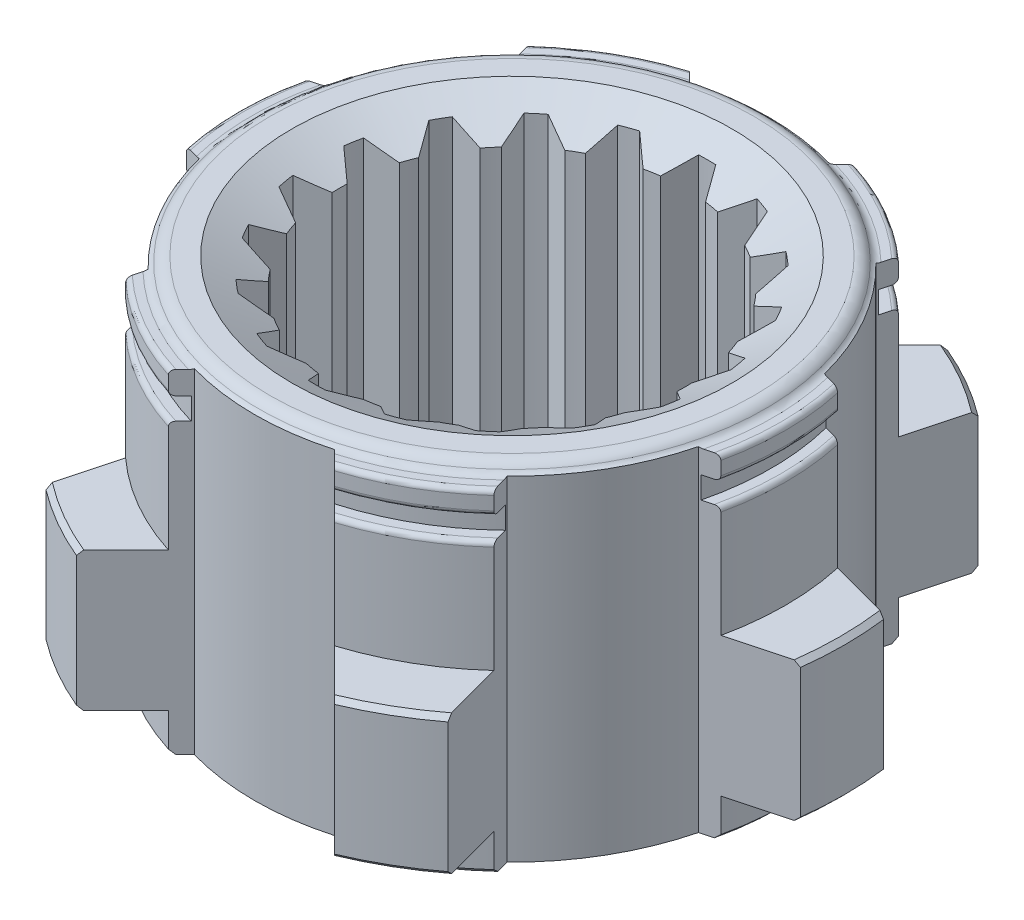
SolidWorks part; units mm, degrees
ref_plane "Plano frontal" through (0, 0, 0) normal (0, 0, 1) x (1, 0, 0)
ref_plane "Plano superior" through (0, 0, 0) normal (0, 1, 0) x (1, 0, 0)
ref_plane "Plano direito" through (0, 0, 0) normal (1, 0, 0) x (0, 0, -1)
sketch "Esboço1" plane through (0, 0, 0) normal (0, 0, 1) x (1, 0, 0)
  line L0 (0, -41.4943) -> (0, 46.6811) construction
  line L1 (18.1, 26.4164) -> (26.8, 26.4164)
  line L2 (26.8, 26.4164) -> (26.8, 25.4164)
  line L3 (26.8, 25.4164) -> (28.7, 25.4164)
  line L4 (28.7, 25.4164) -> (28.7, 23.0164)
  line L5 (28.7, 23.0164) -> (27.2, 23.0164)
  line L6 (27.2, 23.0164) -> (27.2, 20.7164)
  line L7 (27.2, 20.7164) -> (28.7, 20.7164)
  line L8 (28.7, 20.7164) -> (28.7, 9.0164)
  line L9 (28.7, 9.0164) -> (34.9, 9.0164)
  line L10 (34.9, 9.0164) -> (34.9, -5.5836)
  line L11 (34.9, -5.5836) -> (28.7, -5.5836)
  line L12 (28.7, -5.5836) -> (28.7, -9.5836)
  line L13 (28.7, -9.5836) -> (18.1, -9.5836)
  line L14 (18.1, -9.5836) -> (18.1, 26.4164)
  dimension "D1" = 18.1
  dimension "D2" = 26.8
  dimension "D3" = 28.7
  dimension "D4" = 27.2
  dimension "D5" = 28.7
  dimension "D6" = 34.9
  dimension "D7" = 28.7
  dimension "D8" = 1
  dimension "D9" = 2.3
  dimension "D10" = 11.7
  dimension "D11" = 16.4
  dimension "D12" = 14.6
  dimension "D13" = 36
revolve "Revolução1" add sketch "Esboço1" angle 360 about L0
chamfer "Chanfro1" distance 5 angle 30 1 edges at (0, 26.4164, -18.1) first distance on face at (0, 26.4164, -18.1)
chamfer "Chanfro2" distance 5 angle 30 1 edges at (0, -9.5836, -18.1) first distance on face at (0, -9.5836, -28.7)
fillet "Filete1" radius 1.5 1 edges at (0, 26.4164, -26.8)
fillet "Filete2" radius 1 1 edges at (0, 25.4164, -26.8)
fillet "Filete3" radius 0.5 3 edges at (0, 23.0164, -28.7) (0, 25.4164, -28.7) (0, 20.7164, -28.7)
chamfer "Chanfro3" distance 0.5 angle 45 3 edges at (0, -9.5836, -28.7) (0, -5.5836, -34.9) (0, 9.0164, -34.9)
sketch "Esboço2" plane through (0, -9.5836, 0) normal (0, -1, 0) x (1, 0, 0)
  line L0 (0, 0) -> (0, -44.3923) construction
  line L1 (-7.35, -25.9803) -> (-21.8141, -40.4444)
  line L2 (7.35, -25.9803) -> (21.8141, -40.4444)
  line L3 (-21.8141, -40.4444) -> (21.8141, -40.4444)
  line L4 (-26.1746, -6.6249) -> (-45.9329, -1.3307)
  line L5 (-18.8246, -19.3555) -> (-24.1188, -39.1137)
  line L6 (-45.9329, -1.3307) -> (-24.1188, -39.1137)
  line L7 (-18.8246, 19.3555) -> (-24.1188, 39.1137)
  line L8 (-26.1746, 6.6249) -> (-45.9329, 1.3307)
  line L9 (-24.1188, 39.1137) -> (-45.9329, 1.3307)
  line L10 (7.35, 25.9803) -> (21.8141, 40.4444)
  line L11 (-7.35, 25.9803) -> (-21.8141, 40.4444)
  line L12 (21.8141, 40.4444) -> (-21.8141, 40.4444)
  line L13 (26.1746, 6.6249) -> (45.9329, 1.3307)
  line L14 (18.8246, 19.3555) -> (24.1188, 39.1137)
  line L15 (45.9329, 1.3307) -> (24.1188, 39.1137)
  line L16 (18.8246, -19.3555) -> (24.1188, -39.1137)
  line L17 (26.1746, -6.6249) -> (45.9329, -1.3307)
  line L18 (24.1188, -39.1137) -> (45.9329, -1.3307)
  arc A0 (-26.1746, -6.6249) -> (-18.8246, -19.3555) centre (0, 0) ccw
  arc A1 (-7.35, -25.9803) -> (7.35, -25.9803) centre (0, 0) ccw
  arc A2 (-18.8246, 19.3555) -> (-26.1746, 6.6249) centre (0, 0) ccw
  arc A3 (7.35, 25.9803) -> (-7.35, 25.9803) centre (0, 0) ccw
  arc A4 (26.1746, 6.6249) -> (18.8246, 19.3555) centre (0, 0) ccw
  arc A5 (18.8246, -19.3555) -> (26.1746, -6.6249) centre (0, 0) ccw
  dimension "D1" = 6
  dimension "D2" = 90
extrude "Corte-extrusão1" cut sketch "Esboço2" against normal through all
sketch "Esboço3" plane through (0, 26.4164, 0) normal (0, 1, 0) x (1, 0, 0)
  line L0 (-0.9, 20.4802) -> (-2.4697, 17.7614)
  line L1 (0, 0) -> (0, 20.5) construction
  line L2 (0.9, 20.4802) -> (2.4697, 17.7614)
  line L3 (-2.4697, 17.7614) -> (2.4697, 17.7614)
  line L4 (6.1589, 19.5529) -> (3.754, 17.535)
  line L5 (7.8504, 18.9373) -> (8.3955, 15.8456)
  line L6 (3.754, 17.535) -> (8.3955, 15.8456)
  line L7 (12.475, 16.2673) -> (9.5249, 15.1935)
  line L8 (13.8539, 15.1103) -> (13.3087, 12.0185)
  line L9 (9.5249, 15.1935) -> (13.3087, 12.0185)
  line L10 (17.2864, 11.0195) -> (14.147, 11.0195)
  line L11 (18.1864, 9.4607) -> (16.6167, 6.7419)
  line L12 (14.147, 11.0195) -> (16.6167, 6.7419)
  line L13 (20.0128, 4.4427) -> (17.0627, 5.5164)
  line L14 (20.3254, 2.67) -> (17.9204, 0.6521)
  line L15 (17.0627, 5.5164) -> (17.9204, 0.6521)
  line L16 (20.3254, -2.67) -> (17.9204, -0.6521)
  line L17 (20.0128, -4.4427) -> (17.0627, -5.5164)
  line L18 (17.9204, -0.6521) -> (17.0627, -5.5164)
  line L19 (18.1864, -9.4607) -> (16.6167, -6.7419)
  line L20 (17.2864, -11.0195) -> (14.147, -11.0195)
  line L21 (16.6167, -6.7419) -> (14.147, -11.0195)
  line L22 (13.8539, -15.1103) -> (13.3087, -12.0185)
  line L23 (12.475, -16.2673) -> (9.5249, -15.1935)
  line L24 (13.3087, -12.0185) -> (9.5249, -15.1935)
  line L25 (7.8504, -18.9373) -> (8.3955, -15.8456)
  line L26 (6.1589, -19.5529) -> (3.754, -17.535)
  line L27 (8.3955, -15.8456) -> (3.754, -17.535)
  line L28 (0.9, -20.4802) -> (2.4697, -17.7614)
  line L29 (-0.9, -20.4802) -> (-2.4697, -17.7614)
  line L30 (2.4697, -17.7614) -> (-2.4697, -17.7614)
  line L31 (-6.1589, -19.5529) -> (-3.754, -17.535)
  line L32 (-7.8504, -18.9373) -> (-8.3955, -15.8456)
  line L33 (-3.754, -17.535) -> (-8.3955, -15.8456)
  line L34 (-12.475, -16.2673) -> (-9.5249, -15.1935)
  line L35 (-13.8539, -15.1103) -> (-13.3087, -12.0185)
  line L36 (-9.5249, -15.1935) -> (-13.3087, -12.0185)
  line L37 (-17.2864, -11.0195) -> (-14.147, -11.0195)
  line L38 (-18.1864, -9.4607) -> (-16.6167, -6.7419)
  line L39 (-14.147, -11.0195) -> (-16.6167, -6.7419)
  line L40 (-20.0128, -4.4427) -> (-17.0627, -5.5164)
  line L41 (-20.3254, -2.67) -> (-17.9204, -0.6521)
  line L42 (-17.0627, -5.5164) -> (-17.9204, -0.6521)
  line L43 (-20.3254, 2.67) -> (-17.9204, 0.6521)
  line L44 (-20.0128, 4.4427) -> (-17.0627, 5.5164)
  line L45 (-17.9204, 0.6521) -> (-17.0627, 5.5164)
  line L46 (-18.1864, 9.4607) -> (-16.6167, 6.7419)
  line L47 (-17.2864, 11.0195) -> (-14.147, 11.0195)
  line L48 (-16.6167, 6.7419) -> (-14.147, 11.0195)
  line L49 (-13.8539, 15.1103) -> (-13.3087, 12.0185)
  line L50 (-12.475, 16.2673) -> (-9.5249, 15.1935)
  line L51 (-13.3087, 12.0185) -> (-9.5249, 15.1935)
  line L52 (-7.8504, 18.9373) -> (-8.3955, 15.8456)
  line L53 (-6.1589, 19.5529) -> (-3.754, 17.535)
  line L54 (-8.3955, 15.8456) -> (-3.754, 17.535)
  arc A0 (6.1589, 19.5529) -> (7.8504, 18.9373) centre (0, 0) cw
  arc A1 (-0.9, 20.4802) -> (0.9, 20.4802) centre (0, 0) cw
  arc A2 (12.475, 16.2673) -> (13.8539, 15.1103) centre (0, 0) cw
  arc A3 (17.2864, 11.0195) -> (18.1864, 9.4607) centre (0, 0) cw
  arc A4 (20.0128, 4.4427) -> (20.3254, 2.67) centre (0, 0) cw
  arc A5 (20.3254, -2.67) -> (20.0128, -4.4427) centre (0, 0) cw
  arc A6 (18.1864, -9.4607) -> (17.2864, -11.0195) centre (0, 0) cw
  arc A7 (13.8539, -15.1103) -> (12.475, -16.2673) centre (0, 0) cw
  arc A8 (7.8504, -18.9373) -> (6.1589, -19.5529) centre (0, 0) cw
  arc A9 (0.9, -20.4802) -> (-0.9, -20.4802) centre (0, 0) cw
  arc A10 (-6.1589, -19.5529) -> (-7.8504, -18.9373) centre (0, 0) cw
  arc A11 (-12.475, -16.2673) -> (-13.8539, -15.1103) centre (0, 0) cw
  arc A12 (-17.2864, -11.0195) -> (-18.1864, -9.4607) centre (0, 0) cw
  arc A13 (-20.0128, -4.4427) -> (-20.3254, -2.67) centre (0, 0) cw
  arc A14 (-20.3254, 2.67) -> (-20.0128, 4.4427) centre (0, 0) cw
  arc A15 (-18.1864, 9.4607) -> (-17.2864, 11.0195) centre (0, 0) cw
  arc A16 (-13.8539, 15.1103) -> (-12.475, 16.2673) centre (0, 0) cw
  arc A17 (-7.8504, 18.9373) -> (-6.1589, 19.5529) centre (0, 0) cw
  dimension "D1" = 18
extrude "Corte-extrusão2" cut sketch "Esboço3" against normal through all
